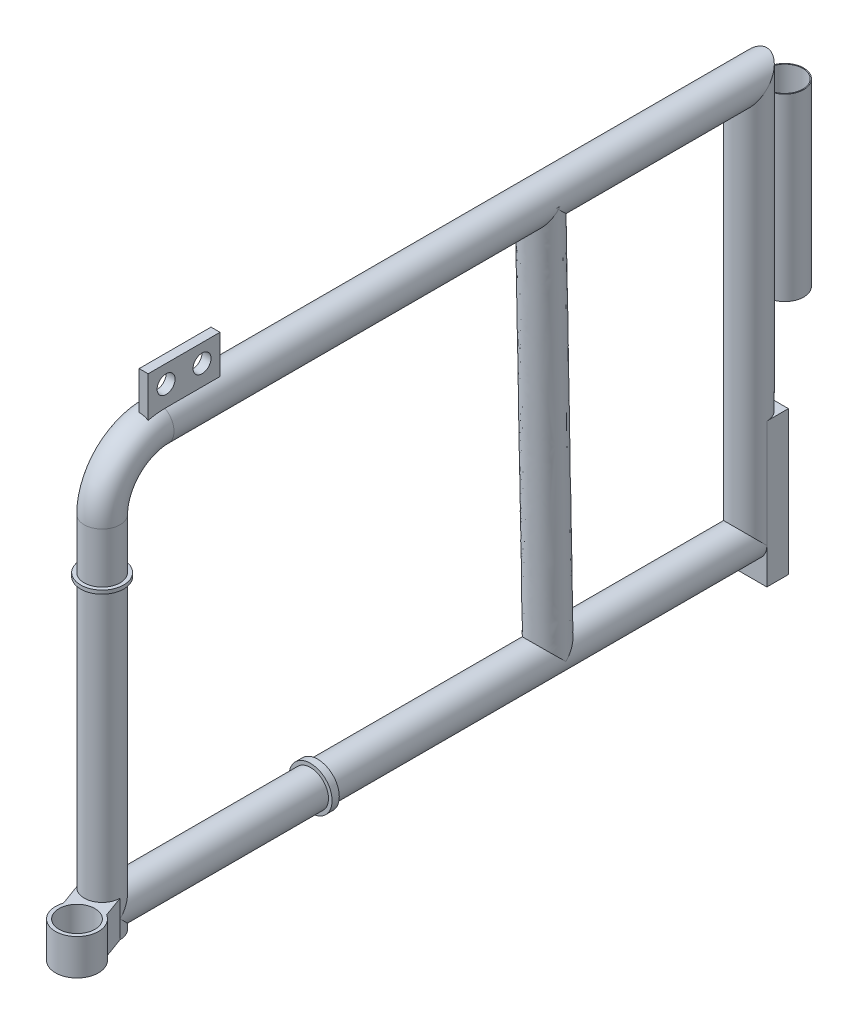
SolidWorks part; units mm, degrees
ref_plane "Front Plane" through (0, 0, 0) normal (0, 0, 1) x (1, 0, 0)
ref_plane "Top Plane" through (0, 0, 0) normal (0, 1, 0) x (1, 0, 0)
ref_plane "Right Plane" through (0, 0, 0) normal (1, 0, 0) x (0, 0, -1)
sketch "Sketch2" plane through (0, 0, 0) normal (0, 0, 1) x (1, 0, 0)
  circle A0 centre (0, 0) radius 12.7
sketch "Sketch3" plane through (0, 0, 0) normal (1, 0, 0) x (0, 0, -1)
  line L0 (0, 0) -> (-457.2, 0)
  line L1 (-457.2, 0) -> (-457.2, 241.3)
  line L2 (-419.1, 279.4) -> (0, 279.4)
  line L3 (0, 279.4) -> (0, 0)
  arc A0 (-419.1, 279.4) -> (-457.2, 241.3) centre (-419.1, 241.3) ccw
  dimension "D1" = 38.1
sweep "Sweep1" add profiles "Sketch2" path "Sketch3"
sketch "Sketch4" plane through (0, 0, 0) normal (1, 0, 0) x (0, 0, -1)
  line L0 (-142.064, 0) -> (-147.3314, 280.7913)
sketch "Sketch5" plane through (0, 0, 0) normal (0, 1, 0) x (1, 0, 0)
  circle A0 centre (0, -142.064) radius 12.7
sweep "Sweep2" add profiles "Sketch5" path "Sketch4"
ref_plane "Plane1" through (0, 0, 304.8) normal (0, 0, 1) x (1, 0, 0)
sketch "Sketch6" plane through (0, 0, 304.8) normal (0, 0, 1) x (1, 0, 0)
  circle A0 centre (0, 0) radius 15.24
extrude "Boss-Extrude1" add sketch "Sketch6" along normal blind 5.08
ref_plane "Plane2" through (0, 0, 279.4) normal (0, 0, 1) x (1, 0, 0)
sketch "Sketch7" plane through (0, 0, 279.4) normal (0, 0, 1) x (1, 0, 0)
  circle A0 centre (0, 279.4) radius 15.24
extrude "Boss-Extrude2" add sketch "Sketch7" along normal blind 5.08
ref_plane "Plane3" through (0, 139.7, 0) normal (0, 1, 0) x (1, 0, 0)
sketch "Sketch8" plane through (0, 139.7, 0) normal (0, 1, 0) x (1, 0, 0)
  line L0 (0, -279.4) -> (0, 25.4) construction
  line L1 (15.24, -279.4) -> (-15.24, -279.4) construction
  circle A0 centre (0, 25.4) radius 12.7
  circle A1 centre (0, 25.4) radius 13.335
extrude "Boss-Extrude3" add sketch "Sketch8" along normal blind 127
sketch "Sketch9" plane through (0, 0, 284.48) normal (0, 0, 1) x (1, 0, 0)
  circle A0 centre (0, 279.4) radius 12.7 construction
  circle A1 centre (0, 279.4) radius 15.24 construction
  circle A2 centre (0, 279.4) radius 12.7
  circle A3 centre (0, 279.4) radius 15.24
extrude "Cut-Extrude1" cut sketch "Sketch9" against normal blind 54.864
sketch "Sketch11" plane through (0, 0, 0) normal (0, 0, 1) x (1, 0, 0)
  line L0 (0, 0) -> (0, -25.4) construction
  line L1 (0, -25.4) -> (-12.7, -25.4)
  line L2 (0, -25.4) -> (12.7, -25.4)
  line L3 (12.7, -25.4) -> (12.7, 76.2)
  line L4 (12.7, 0) -> (12.7, 279.4) construction
  line L5 (12.7, 76.2) -> (-12.7, 76.2)
  line L6 (-12.7, 279.4) -> (-12.7, 0) construction
  line L7 (-12.7, 76.2) -> (-12.7, -25.4)
extrude "Boss-Extrude4" add sketch "Sketch11" against normal blind 15.24
ref_plane "Plane4" through (0, -12.7, 0) normal (0, 1, 0) x (1, 0, 0)
sketch "Sketch14" plane through (0, -12.7, 0) normal (0, 1, 0) x (1, 0, 0)
  line L0 (12.7, -457.2) -> (18.1456, -472.1617)
  line L1 (-9.7288, -465.3634) -> (-4.2832, -480.3251)
  circle A0 centre (0, -457.2) radius 12.7 construction
  arc A1 (-4.2832, -480.3251) -> (18.1456, -472.1617) centre (10.1729, -485.1499) ccw
  arc A2 (12.7, -457.2) -> (-9.7288, -465.3634) centre (0, -457.2) ccw
extrude "Boss-Extrude5" add sketch "Sketch14" along normal blind 25.4
sketch "Sketch15" plane through (0, 12.7, 0) normal (0, 1, 0) x (1, 0, 0)
  circle A0 centre (10.1729, -485.1499) radius 12.7
extrude "Cut-Extrude2" cut sketch "Sketch15" against normal through all
fillet "Fillet1" radius 12.7 rebuild error yes
ref_plane "Plane5" through (0, 279.4, 0) normal (0, 1, 0) x (1, 0, 0)
sketch "Sketch16" plane through (0, 279.4, 0) normal (0, 1, 0) x (1, 0, 0)
  line L0 (0, -469.9) -> (0, -431.038) construction
  line L1 (0, -431.038) -> (6.35, -431.038)
  line L2 (6.35, -431.038) -> (6.35, -380.238)
  line L3 (6.35, -380.238) -> (0, -380.238)
  line L4 (0, -380.238) -> (0, -431.038)
  arc A0 (-12.7, -457.2) -> (12.7, -457.2) centre (0, -457.2) ccw construction
extrude "Boss-Extrude6" add sketch "Sketch16" along normal blind 38.1
sketch "Sketch17" plane through (6.35, 0, 0) normal (1, 0, 0) x (0, 0, -1)
  line L0 (-380.238, 317.5) -> (-380.238, 292.1) construction
  line L1 (-380.238, 317.5) -> (-380.238, 290.3985) construction
  line L2 (-380.238, 290.3985) -> (-380.238, 292.1) construction
  line L3 (-405.638, 304.8) -> (-431.038, 304.8) construction
  line L4 (-431.038, 317.5) -> (-431.038, 288.9251) construction
  line L5 (-405.638, 304.8) -> (-405.638, 317.5) construction
  line L6 (-431.038, 317.5) -> (-380.238, 317.5) construction
  circle A0 centre (-418.338, 304.8) radius 6.35
  circle A1 centre (-392.938, 304.8) radius 6.35
extrude "Cut-Extrude3" cut sketch "Sketch17" against normal blind 38.1
ref_plane "Plane6" through (0, 203.2, 0) normal (0, 1, 0) x (1, 0, 0)
sketch "Sketch18" plane through (0, 203.2, 0) normal (0, 1, 0) x (1, 0, 0)
  circle A0 centre (0, -457.2) radius 15.24
extrude "Boss-Extrude7" add sketch "Sketch18" along normal blind 2.54
